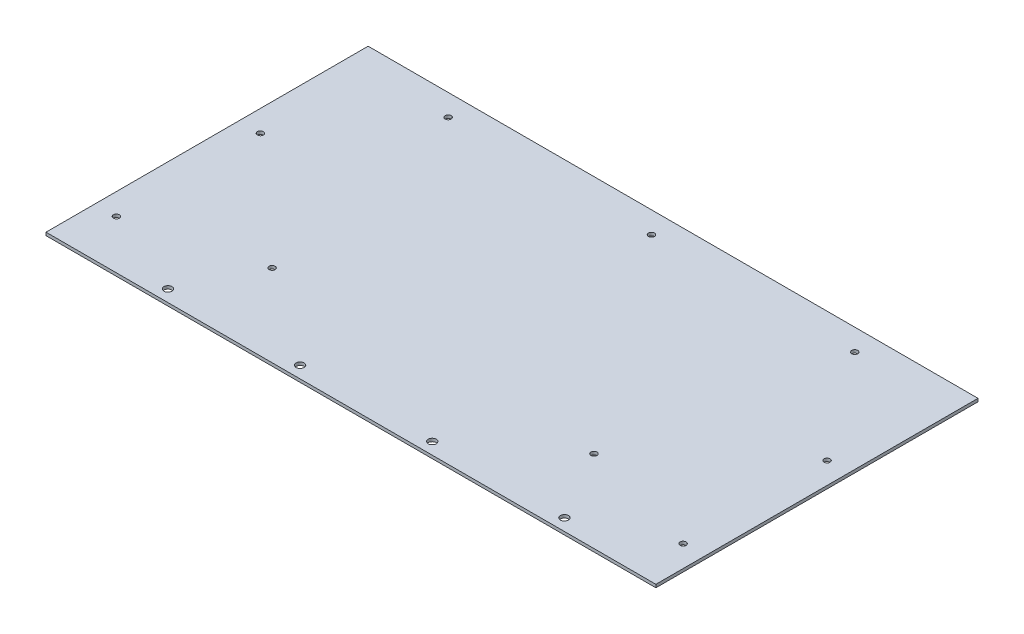
SolidWorks part; units mm, degrees
material "6061-T6 (SS)"
ref_plane "X-Y Datum" through (0, 0, 0) normal (0, 0, 1) x (1, 0, 0)
ref_plane "X-Z Datum" through (0, 0, 0) normal (0, 1, 0) x (1, 0, 0)
ref_plane "Y-Z Datum" through (0, 0, 0) normal (1, 0, 0) x (0, 0, -1)
sketch "Sketch1" plane through (0, 0, 0) normal (0, 0, 1) x (1, 0, 0)
  line L1 (-228.6, -1.143) -> (228.6, -1.143)
  line L2 (-228.6, -1.143) -> (-228.6, 1.143)
  line L3 (-228.6, 1.143) -> (228.6, 1.143)
  line L4 (228.6, -1.143) -> (228.6, 1.143)
  line L5 (-228.6, -1.143) -> (228.6, 1.143) construction
  line L6 (-228.6, 1.143) -> (228.6, -1.143) construction
  point P0 (0, 0)
  dimension "D1" = 2.286
  dimension "D2" = 457.2
extrude "Boss-Extrude1" add sketch "Sketch1" along normal blind 238.3152
sketch "Sketch2" plane through (0, 0, 0) normal (0, 0, -1) x (-1, 0, 0)
  line L22 (-228.6, 1.143) -> (-228.6, -1.143)
  line L23 (-228.6, -1.143) -> (228.6, -1.143)
  line L24 (228.6, -1.143) -> (228.6, 1.143)
  line L25 (228.6, 1.143) -> (-228.6, 1.143)
  line L26 (-228.6, 1.143) -> (-228.6, -1.143)
  line L27 (-228.6, -1.143) -> (228.6, -1.143)
  line L28 (228.6, -1.143) -> (228.6, 1.143)
  line L29 (228.6, 1.143) -> (-228.6, 1.143)
  line M6 (-228.6, -1.143) -> (228.6, -1.143)
  line M8 (228.6, 1.143) -> (-228.6, 1.143)
  dimension "D1" = 0
extrude "Boss-Extrude2" add sketch "Sketch2" along normal blind 3.175 contours M8 M6 | M8 M6 region at (0, 0, 0)
sketch "Sketch9" plane through (0, 1.143, 0) normal (0, 1, 0) x (1, 0, 0)
  line L0 (-146.05, -238.3152) -> (-146.05, -229.4252) construction
  line L1 (228.6, -238.3152) -> (-228.6, -238.3152) construction
  line L2 (-228.6, -238.3152) -> (-228.6, 3.175) construction
  circle A0 centre (-146.05, -229.4252) radius 3
  dimension "D2" = 82.55
  dimension "D3" = 6
  dimension "D1" = 8.89
extrude "Cut-Extrude10" cut sketch "Sketch9" against normal blind 2.54
pattern_linear "LPattern1" count 4 spacing 99.06 along (1, 0, 0) of "Cut-Extrude10"
sketch "Sketch10" plane through (0, -1.143, 0) normal (0, -1, 0) x (1, 0, 0)
  circle A0 centre (151.13, 229.4252) radius 3 construction
  circle A1 centre (52.07, 229.4252) radius 3 construction
  circle A2 centre (-46.99, 229.4252) radius 3 construction
  circle A3 centre (-146.05, 229.4252) radius 3 construction
  circle A4 centre (151.13, 229.4252) radius 3
  circle A5 centre (52.07, 229.4252) radius 3
  circle A6 centre (-46.99, 229.4252) radius 3
  circle A7 centre (-146.05, 229.4252) radius 3
sketch "Sketch12" plane through (0, -1.143, 0) normal (0, -1, 0) x (1, 0, 0)
  point P0 (-212.419, 93.7748)
  point P1 (-152.4, 13.0175)
  point P3 (0, 13.0175)
  point P5 (152.4, 13.0175)
  point P7 (212.419, 93.7748)
  point P9 (212.419, 201.7248)
  point P17 (-212.419, 201.7248)
  point P27 (-120.65, 176.776)
  point P31 (120.65, 176.776)
hole_wizard "M4 Clearance Hole1" positions "Sketch12" profile "Sketch13" hole size "M4" standard "ANSI Metric" end condition through all
sketch "Sketch13" plane through (-212.419, -1.143, 93.7748) normal (1, 0, 0) x (0, 0, -1)
  line L0 (0, 0) -> (0, 2.286)
  line L1 (0, 2.286) -> (2.25, 2.286)
  line L2 (2.25, 2.286) -> (2.25, 0)
  line L5 (2.25, 0) -> (0, 0)
  line L11 (0, -6.35) -> (0, 107.95) construction
  dimension "Thru Hole Dia." = 4.5
  dimension "Thru Hole Depth" = 2.286
